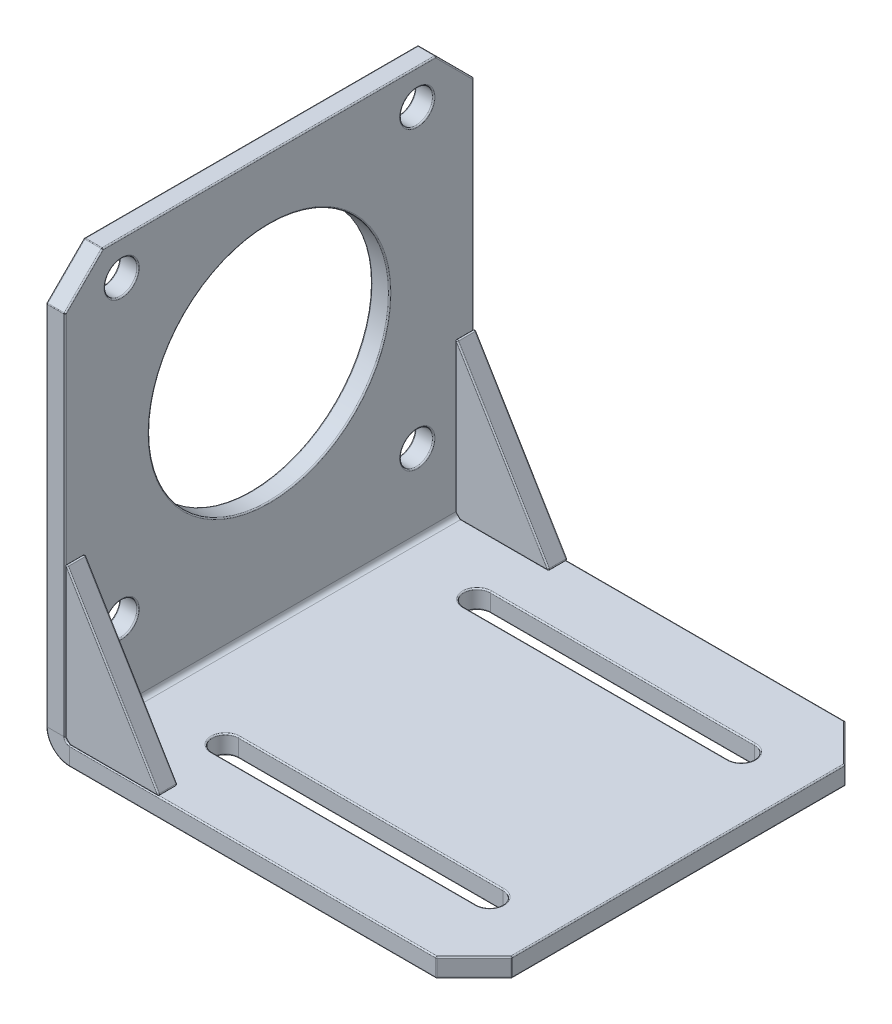
SolidWorks part; units mm, degrees
note: The reader was unsure of these and kept them because the rebuilt part matched: flange length of "Bordo-Flangia1".
ref_plane "Piano frontale" through (0, 0, 0) normal (0, 0, 1) x (1, 0, 0)
ref_plane "Piano superiore" through (0, 0, 0) normal (0, 1, 0) x (1, 0, 0)
ref_plane "Piano destro" through (0, 0, 0) normal (1, 0, 0) x (0, 0, -1)
sketch "Schizzo1" plane through (0, 0, 0) normal (0, 0, 1) x (1, 0, 0)
  line L0 (0, 0) -> (68, 0)
  dimension "D1" = 68
base flange "Base-Flangia1" sketch "Schizzo1" end condition mid plane depth 65 reverse direction no thickness 3 reverse thickness direction no bend radius 0.7366
edge flange "Bordo-Flangia1" sketch "Schizzo8" flange angle 90 flange length 68 flange position material inside bend radius 0.7366 thickness 3 parameters "D6"=10
sketch "Schizzo8" plane through (0, 0, 0) normal (-1, 0, 0) x (0, 0, 1)
  line L0 (32.5, 0) -> (-32.5, 0) construction
  line L1 (32.5, 0) -> (-32.5, 0)
  line L2 (-32.5, 0) -> (-32.5, 65)
  line L3 (-32.5, 65) -> (32.5, 65)
  line L4 (32.5, 65) -> (32.5, 0)
  line L5 (32.5, -3) -> (-32.5, -3) construction
  point P6 (0, -3)
  dimension "D1" = 68
bend "PiegaturaBordo1" bend radius 0.7366 bend angle 90 parameters "D5"=1
sketch "Schizzo10" plane through (3, 0, 0) normal (1, 0, 0) x (0, 0, -1)
  line L0 (0, 65) -> (0, 0.7366) construction
  line L1 (-32.5, 65) -> (32.5, 65) construction
  line L2 (32.5, 0.7366) -> (-32.5, 0.7366) construction
  line L3 (32.5, 36) -> (-32.5, 36) construction
  line L4 (32.5, 65) -> (32.5, 0.7366) construction
  line L5 (-32.5, 0.7366) -> (-32.5, 65) construction
  circle A0 centre (0, 36) radius 19.1
  circle A1 centre (-23.5, 59.5) radius 2.6
  circle A2 centre (23.5, 59.5) radius 2.6
  circle A3 centre (-23.5, 12.5) radius 2.6
  circle A4 centre (23.5, 12.5) radius 2.6
  dimension "D1" = 38.2
  dimension "D2" = 29
  dimension "D3" = 5.2
  dimension "D4" = 47
  dimension "D5" = 47
extrude "Taglio-Estrusione1" cut sketch "Schizzo10" against normal through all normal cut yes
sketch "Schizzo12" plane through (0, 0, 0) normal (0, 1, 0) x (1, 0, 0)
  line L0 (68, 0) -> (0, 0) construction
  line L1 (68, -32.5) -> (68, 32.5) construction
  line L2 (68, 20) -> (0, 20) construction
  line L3 (68, -20) -> (0, -20) construction
  line L4 (31, 17.893) -> (31, -25.3654) construction
  line L5 (16, 17.893) -> (16, -25.3654) construction
  line L6 (58, 17.893) -> (58, -25.3654) construction
  line L7 (58, 20) -> (16, 20) construction
  line L8 (58, 17.9) -> (16, 17.9)
  line L9 (58, 22.1) -> (16, 22.1)
  line L10 (58, -20) -> (16, -20) construction
  line L11 (58, -22.1) -> (16, -22.1)
  line L12 (58, -17.9) -> (16, -17.9)
  line L13 (68, -32.5) -> (68, 32.5) construction
  line L14 (3.7366, -32.5) -> (68, -32.5) construction
  arc A0 (58, 17.9) -> (58, 22.1) centre (58, 20) ccw
  arc A1 (16, 22.1) -> (16, 17.9) centre (16, 20) ccw
  arc A2 (58, -22.1) -> (58, -17.9) centre (58, -20) ccw
  arc A3 (16, -17.9) -> (16, -22.1) centre (16, -20) ccw
  point P17 (37, 20)
  point P22 (37, -20)
  dimension "D5" = 10
  dimension "D3" = 4.2
  dimension "D2" = 42
  dimension "D4" = 20
  dimension "D1" = 40
extrude "Taglio-Estrusione3" cut sketch "Schizzo12" against normal through all normal cut yes
sketch "Schizzo15" plane through (0, 0, 0) normal (0, 0, 1) x (1, 0, 0)
  line L0 (0, 25) -> (5.1835, 25) construction
  line L1 (0, 0.7366) -> (0, 65) construction
  line L2 (18, -3) -> (18, 2.1352) construction
  line L3 (3.7366, -3) -> (68, -3) construction
  line L4 (13.7349, 0) -> (-1.1225, 0) construction
  line L5 (58, 0) -> (16, 0) construction
  line L6 (3, 25) -> (3, -3.5666) construction
  line L7 (3, 0.7366) -> (3, 65) construction
  line L8 (3, 25) -> (18, 0)
  line L9 (18, 0) -> (3.7366, 0)
  line L10 (3.7366, 0) -> (3, 0.7366)
  line L11 (3, 0.7366) -> (3, 25)
  dimension "D1" = 15
  dimension "D2" = 25
extrude "Estrusione-Estrusione3" add sketch "Schizzo15" against normal blind 3 from surface at 32.5 separate body starting at face at (1.5, 32.8683, 32.5)
mirror "Specchia5" about plane through (0, 0, 0) normal (0, 0, 1) of bodies 109
chamfer "Smusso1" distance 6 angle 45 4 edges at (68, -1.5, 32.5) (68, -1.5, -32.5) (1.5, 65, -32.5) (1.5, 65, 32.5)
fillet "Raccordo1" radius 0.2 58 edges at (68, 0, 0) (68, -3, 0) (68, -1.5, -26.5) (68, -1.5, 26.5) (65, -3, -29.5) (65, -3, 29.5) (62, -1.5, 32.5) (65, 0, -29.5) (65, 0, 29.5) (62, -1.5, -32.5) (0, 29.8683, -32.5) (3, 29.8683, -32.5) (1.5, 59, -32.5) (3, 65, 0) (3, 62, 29.5) (3, 62, -29.5) (32.8683, -3, -32.5) (0, 65, 0) (1.5, 65, 26.5) (1.5, 65, -26.5) (0, 62, 29.5) (32.8683, 0, -32.5) (0, 62, -29.5) (1.5, 59, 32.5) (32.8683, -3, 32.5) (32.8683, 0, 32.5) (1.0944, -1.9056, -32.5) (1.0944, -1.9056, 32.5) (3.2157, 0.2157, -32.5) (3.2157, 0.2157, 32.5) (3, 29.8683, 32.5) (0, 29.8683, 32.5) (0, 15.1, -23.5) (3, 15.1, -23.5) (0, 9.9, 23.5) (3, 9.9, 23.5) (0, 56.9, -23.5) (3, 56.9, -23.5) (0, 62.1, 23.5) (3, 62.1, 23.5) (0, 55.1, 0) (3, 55.1, 0) (60.1, -3, -20) (37, -3, -17.9) (13.9, -3, -20) (37, -3, -22.1) (60.1, 0, -20) (37, 0, -22.1) (13.9, 0, -20) (37, 0, -17.9) (60.1, -3, 20) (37, -3, 22.1) (13.9, -3, 20) (37, -3, 17.9) (60.1, 0, 20) (37, 0, 17.9) (13.9, 0, 20) (37, 0, 22.1)
fillet "Raccordo2" radius 0.2 10 edges at (3.3683, 0.3683, -29.5) (3, 12.8683, -29.5) (10.8683, 0, -29.5) (18, 0, -31) (10.5, 12.5, -29.5) (3, 25, -31) (10.5, 12.5, -32.5) (3, 12.8683, -32.5) (3.3683, 0.3683, -32.5) (10.8683, 0, -32.5)
fillet "Raccordo3" radius 0.2 10 edges at (3.3683, 0.3683, 32.5) (3, 12.8683, 32.5) (10.8683, 0, 32.5) (3, 25, 31) (18, 0, 31) (10.5, 12.5, 32.5) (10.5, 12.5, 29.5) (3, 12.8683, 29.5) (3.3683, 0.3683, 29.5) (10.8683, 0, 29.5)
sketch "Linee di piegatura1" [suppressed] plane through (0, 0, 0) normal (0, 1, 0) x (1, 0, 0)
sketch "Casella di contorno1" [suppressed] plane through (0, 0, 0) normal (0, 1, 0) x (1, 0, 0)
sheet metal parameters "Lamiera1" thickness 3 parameters "D1"=0.7366
flat pattern "Ripetizione piatta1" [suppressed]
sketch "Linee di piegatura2" plane through (0, 0, 0) normal (0, 1, 0) x (1, 0, 0)
sketch3d "Casella di contorno2" [suppressed]
  line L0 (0, 41.3, 0) -> (0, 0, 0) construction
  line L1 (35, 41.3, 0) -> (35, 0, 0) construction
  line L2 (0, 41.3, 0) -> (35, 41.3, 0) construction
  line L3 (0, 0, 0) -> (35, 0, 0) construction
sheet metal parameters "Lamiera2" thickness 3 parameters "D1"=0.7366
flat pattern "Ripetizione piatta1"
sketch "Linee di piegatura2" plane through (0, 0, 0) normal (0, 1, 0) x (1, 0, 0)
  line L0 (1.98, -25) -> (1.98, 25) construction
  line L1 (1.98, -25) -> (1.98, 25) construction
sketch3d "Casella di contorno2" [suppressed]
  line L0 (53, 0, 0) -> (-47.04, 0, 0) construction
  line L1 (53, 50, 0) -> (-47.04, 50, 0) construction
  line L2 (53, 0, 0) -> (53, 50, 0) construction
  line L3 (-47.04, 0, 0) -> (-47.04, 50, 0) construction
bend of the flat pattern "Appiattito-<PiegaturaBordo1>1"
sheet metal parameters "Lamiera3" thickness 3 parameters "D1"=0.7366
flat pattern "Ripetizione piatta1"
sketch "Linee di piegatura2" plane through (0, 0, 0) normal (0, 1, 0) x (1, 0, 0)
  line L0 (1.98, -32.5) -> (1.98, 32.5) construction
  line L1 (1.98, -32.5) -> (1.98, 32.5) construction
sketch3d "Casella di contorno2" [suppressed]
  line L0 (68, 0, 0) -> (-64.04, 0, 0) construction
  line L1 (68, 65, 0) -> (-64.04, 65, 0) construction
  line L2 (68, 0, 0) -> (68, 65, 0) construction
  line L3 (-64.04, 0, 0) -> (-64.04, 65, 0) construction
bend of the flat pattern "Appiattito-<PiegaturaBordo1>1"
sheet metal parameters "Lamiera11" thickness 3 parameters "D1"=0.7366
flat pattern "Ripetizione piatta1"
sketch "Linee di piegatura2" plane through (0, 0, 0) normal (0, 1, 0) x (1, 0, 0)
  line L0 (1.98, -32.3) -> (1.98, 32.3) construction
  line L1 (1.98, -32.3) -> (1.98, 32.3) construction
sketch3d "Casella di contorno2" [suppressed]
  line L0 (-64.04, 0, 0) -> (68, 0, 0) construction
  line L1 (-64.04, 65, 0) -> (68, 65, 0) construction
  line L2 (-64.04, 0, 0) -> (-64.04, 65, 0) construction
  line L3 (68, 0, 0) -> (68, 65, 0) construction
bend of the flat pattern "Appiattito-<PiegaturaBordo1>1"
